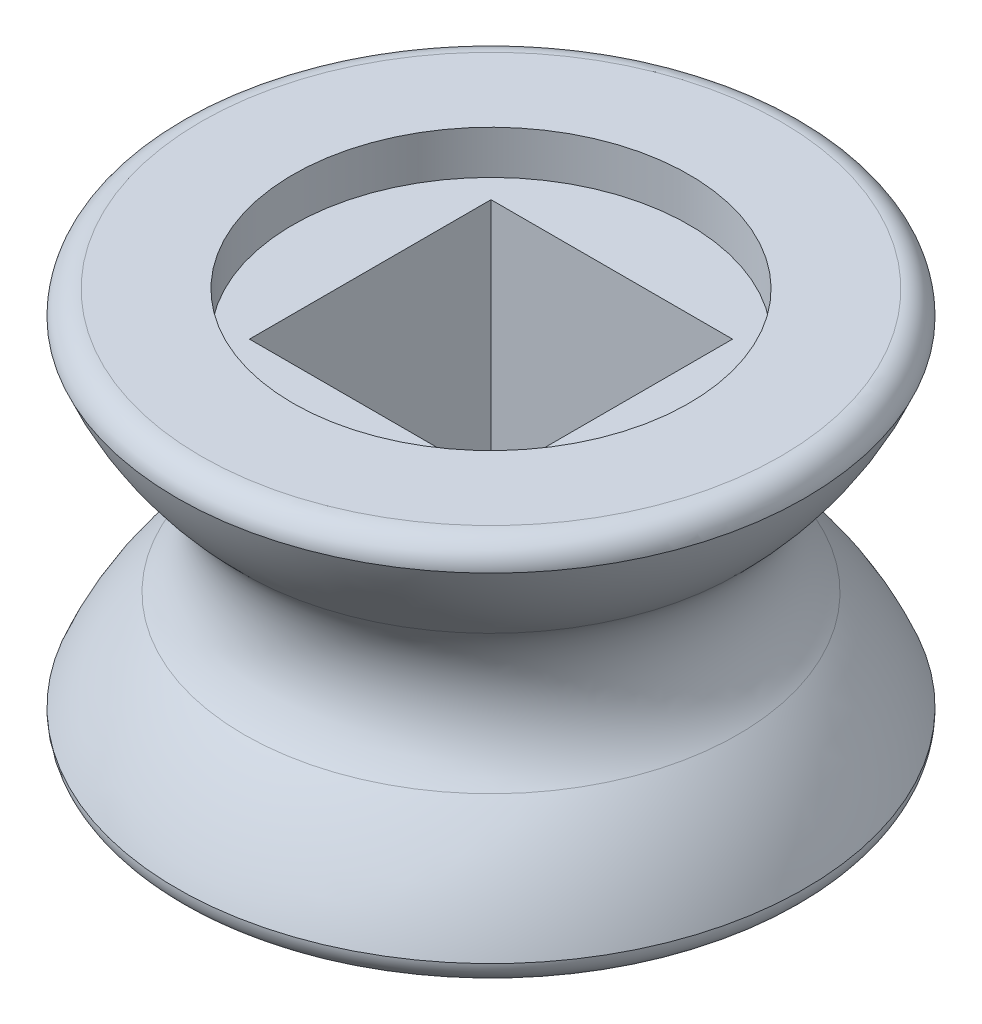
SolidWorks part; units mm, degrees
ref_plane "Front Plane" through (0, 0, 0) normal (0, 0, 1) x (1, 0, 0)
ref_plane "Top Plane" through (0, 0, 0) normal (0, 1, 0) x (1, 0, 0)
ref_plane "Right Plane" through (0, 0, 0) normal (1, 0, 0) x (0, 0, -1)
sketch "Sketch1" plane through (0, 0, 0) normal (0, 0, 1) x (1, 0, 0)
  line L0 (0, -5.08) -> (0, 5.08) construction
  line L1 (8.255, -2.54) -> (8.255, -5.08)
  line L2 (8.255, -5.08) -> (0, -5.08)
  line L3 (8.255, 2.54) -> (8.255, 5.08)
  line L4 (8.255, 5.08) -> (0, 5.08)
  line L5 (0, -5.08) -> (0, 5.08)
  arc A0 (8.255, 2.54) -> (8.255, -2.54) centre (8.255, 0) ccw
  dimension "D2" = 5.08
  dimension "D1" = 10.16
  dimension "D3" = 8.255
revolve "Revolve1" add sketch "Sketch1" angle 360 about L0
sketch "Sketch3" plane through (0, 5.08, 0) normal (0, 1, 0) x (1, 0, 0)
  line L1 (-3.175, -3.175) -> (3.175, -3.175)
  line L2 (-3.175, -3.175) -> (-3.175, 3.175)
  line L3 (-3.175, 3.175) -> (3.175, 3.175)
  line L4 (3.175, -3.175) -> (3.175, 3.175)
  line L5 (-3.175, -3.175) -> (3.175, 3.175) construction
  line L6 (-3.175, 3.175) -> (3.175, -3.175) construction
  point P0 (0, 0)
  dimension "D1" = 6.35
extrude "Cut-Extrude2" cut sketch "Sketch3" against normal through all
sketch "Sketch4" plane through (0, 5.08, 0) normal (0, 1, 0) x (1, 0, 0)
  circle A0 centre (0, 0) radius 5.207
  dimension "D1" = 10.414
extrude "Cut-Extrude3" cut sketch "Sketch4" against normal blind 1.143
mirror "Mirror1" about plane through (0, 0, 0) normal (0, 1, 0) of "Cut-Extrude3"
fillet "Fillet1" radius 0.635 2 edges at (0, -5.08, -8.255) (0, 5.08, -8.255)
fillet "Fillet2" radius 7.62 2 edges at (0, -2.54, -8.255) (0, 2.54, -8.255)
